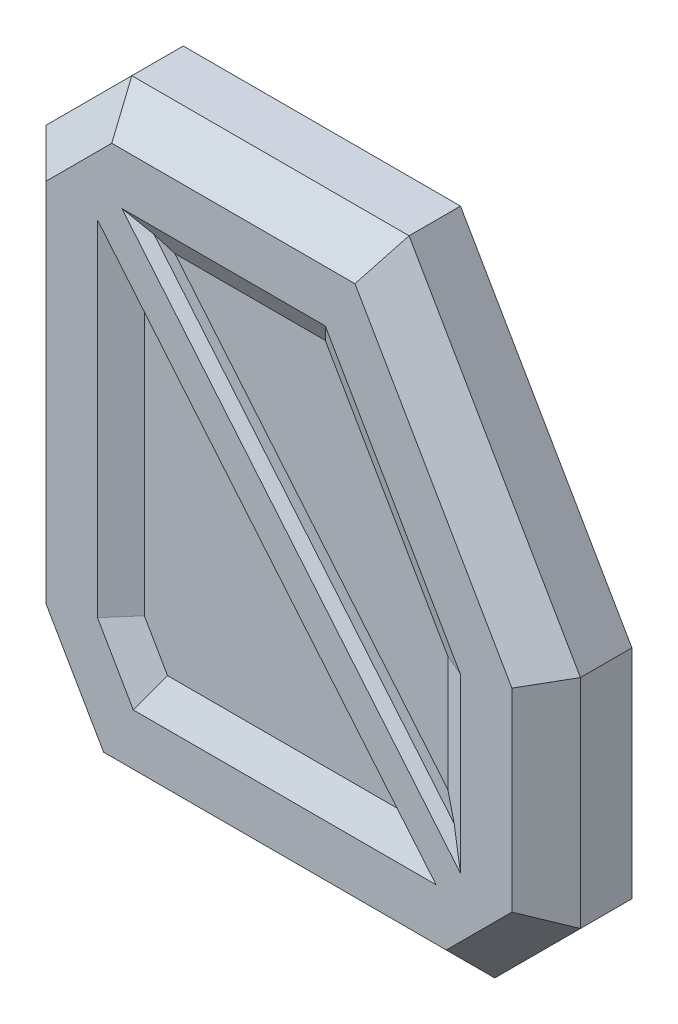
SolidWorks part; units mm, degrees
ref_plane "Plan de face" through (0, 0, 0) normal (0, 0, 1) x (1, 0, 0)
ref_plane "Plan de dessus" through (0, 0, 0) normal (0, 1, 0) x (1, 0, 0)
ref_plane "Plan de droite" through (0, 0, 0) normal (1, 0, 0) x (0, 0, -1)
sketch "Esquisse1" plane through (0, 0, 0) normal (0, 0, 1) x (1, 0, 0)
  line L0 (0, 0) -> (219.726, 0)
  line L1 (219.726, 0) -> (269.726, 50)
  line L2 (269.726, 50) -> (269.726, 176.7949)
  line L3 (269.726, 176.7949) -> (169.726, 350)
  line L4 (169.726, 350) -> (8, 350)
  line L5 (8, 350) -> (-42, 300)
  line L6 (-42, 300) -> (-42, 72.7461)
  line L7 (-42, 72.7461) -> (0, 0)
  line L8 (269.726, 176.7949) -> (269.726, 350) construction
  line L9 (269.726, 350) -> (169.726, 350) construction
  line L10 (8, 350) -> (-42, 350) construction
  line L11 (-42, 350) -> (-42, 300) construction
  line L12 (-42, 72.7461) -> (-42, 0) construction
  line L13 (-42, 0) -> (0, 0) construction
  line L14 (269.726, 50) -> (269.726, 0) construction
  line L15 (269.726, 0) -> (219.726, 0) construction
  dimension "D1" = 350
  dimension "D2" = 311.726
  dimension "D3" = 30
  dimension "D4" = 45
  dimension "D5" = 50
  dimension "D6" = 173.2051
  dimension "D7" = 50
  dimension "D8" = 72.7461
extrude "Boss.-Extru.1" add sketch "Esquisse1" along normal blind 50
chamfer "Chanfrein1" distance 20 angle 45 8 edges at (-42, 186.3731, 50) (-17, 325, 50) (88.863, 350, 50) (219.726, 263.3975, 50) (269.726, 113.3975, 50) (244.726, 25, 50) (109.863, 0, 50) (-21, 36.3731, 50)
sketch "Esquisse2" plane through (0, 0, 50) normal (0, 0, 1) x (1, 0, 0)
  line L8 (28.7107, 300) -> (219.726, 70.7107)
  line L9 (199.0153, 50) -> (8, 279.2893)
  line L16 (28.7107, 300) -> (8, 279.2893)
  line L17 (8, 279.2893) -> (8, 86.1436)
  line L18 (8, 86.1436) -> (28.8675, 50)
  line L19 (28.8675, 50) -> (199.0153, 50)
  line L20 (199.0153, 50) -> (219.726, 70.7107)
  line L21 (219.726, 70.7107) -> (219.726, 163.3975)
  line L22 (219.726, 163.3975) -> (140.8585, 300)
  line L23 (140.8585, 300) -> (28.7107, 300)
  line L24 (28.7107, 300) -> (8, 279.2893) construction
  line L25 (8, 279.2893) -> (8, 86.1436)
  line L26 (8, 86.1436) -> (28.8675, 50)
  line L27 (28.8675, 50) -> (199.0153, 50)
  line L28 (199.0153, 50) -> (219.726, 70.7107) construction
  line L29 (219.726, 70.7107) -> (219.726, 163.3975)
  line L30 (219.726, 163.3975) -> (140.8585, 300)
  line L31 (140.8585, 300) -> (28.7107, 300)
  dimension "D1" = 30
extrude "Enlèv. mat.-Extru.1" cut sketch "Esquisse2" against normal blind 10
chamfer "Chanfrein2" distance 10 angle 60 6 edges at (219.726, 117.0541, 40) (180.2923, 231.6987, 40) (84.7846, 300, 40) (113.9414, 50, 40) (18.4338, 68.0718, 40) (8, 182.7165, 40) first distance on face at (219.726, 117.0541, 45) first distance on face at (180.2923, 231.6987, 45) first distance on face at (84.7846, 300, 45) first distance on face at (113.9414, 50, 45) first distance on face at (18.4338, 68.0718, 45) first distance on face at (8, 182.7165, 45)
chamfer "Chanfrein3" distance 5 angle 45 2 edges at (103.5077, 164.6447, 50) (124.2184, 185.3553, 50)
sketch "Esquisse3" plane through (0, 0, 0) normal (0, 0, -1) x (-1, 0, 0)
  line L16 (-5.7735, 10) -> (32, 75.4256)
  line L17 (32, 75.4256) -> (32, 295.8579)
  line L18 (32, 295.8579) -> (-12.1421, 340)
  line L19 (-12.1421, 340) -> (-163.9525, 340)
  line L20 (-163.9525, 340) -> (-259.726, 174.1154)
  line L21 (-259.726, 174.1154) -> (-259.726, 54.1421)
  line L22 (-259.726, 54.1421) -> (-215.5839, 10)
  line L23 (-215.5839, 10) -> (-5.7735, 10)
  line L24 (-5.7735, 10) -> (32, 75.4256)
  line L25 (32, 75.4256) -> (32, 295.8579)
  line L26 (32, 295.8579) -> (-12.1421, 340)
  line L27 (-12.1421, 340) -> (-163.9525, 340)
  line L28 (-163.9525, 340) -> (-259.726, 174.1154)
  line L29 (-259.726, 174.1154) -> (-259.726, 54.1421)
  line L30 (-259.726, 54.1421) -> (-215.5839, 10)
  line L31 (-215.5839, 10) -> (-5.7735, 10)
  dimension "D1" = 10
extrude "Enlèv. mat.-Extru.2" cut sketch "Esquisse3" against normal blind 30
